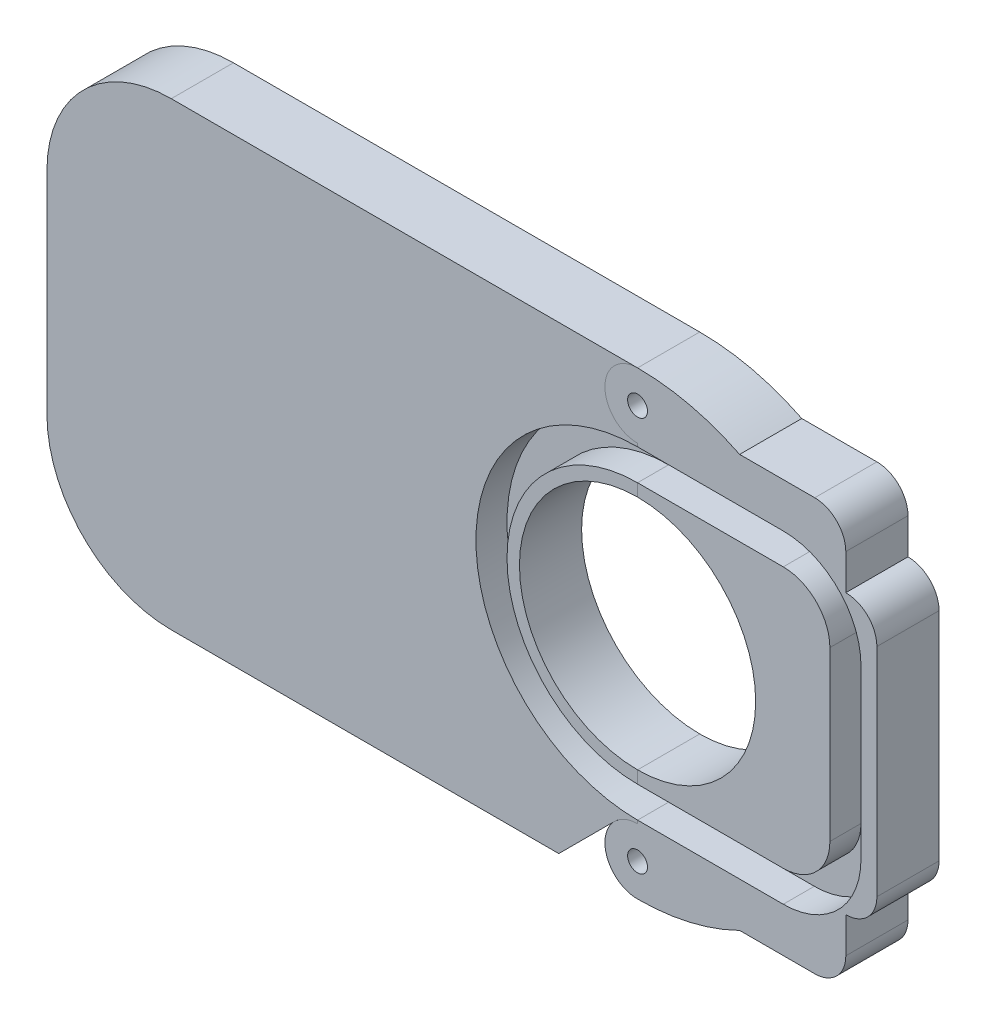
SolidWorks part; units mm, degrees
note: The reader was unsure of these and kept them because the rebuilt part matched: shared geometry of "Sketch1<6>".
material "Сталь 08кп ГОСТ 535-88"
ref_plane "Спереди" through (0, 0, 0) normal (0, 0, 1) x (1, 0, 0)
ref_plane "Сверху" through (0, 0, 0) normal (0, 1, 0) x (1, 0, 0)
ref_plane "Справа" through (0, 0, 0) normal (1, 0, 0) x (0, 0, -1)
sketch "Sketch1" plane through (0, 0, 0) normal (0, 0, 1) x (1, 0, 0)
  line L0 (-51.8389, -200.705) -> (-60.8012, -209.6673)
  line L1 (-14.6282, -195.0926) -> (-14.6282, -200.824)
  line L2 (-19.6282, -205.824) -> (-31.7061, -205.824)
  line L3 (-14.6266, -150.2409) -> (-14.6266, -144.5103)
  line L4 (-19.6266, -139.5103) -> (-31.7068, -139.5103)
  line L26 (-9.6282, -190.0926) -> (-9.6282, -155.2396)
  line L27 (-143.1333, -155.6673) -> (-143.1333, -189.6673)
  line L28 (-123.1333, -209.6673) -> (-60.8012, -209.6673)
  line L32 (-48.1266, -135.6673) -> (-123.1333, -135.6673)
  line L33 (-48.1266, -153.6673) -> (-48.1266, -146.1673)
  line L34 (-48.1266, -199.1673) -> (-48.1266, -191.6673)
  arc A0 (-48.1266, -146.1673) -> (-48.1266, -135.6673) centre (-48.1266, -140.9173) cw
  circle A1 centre (-48.1266, -140.9173) radius 1.6
  arc A2 (-48.1266, -209.6673) -> (-48.1266, -199.1673) centre (-48.1266, -204.4173) cw
  circle A3 centre (-48.1266, -204.4173) radius 1.6
  arc A4 (-14.6266, -144.5103) -> (-19.6266, -139.5103) centre (-19.6266, -144.5103) ccw
  arc A5 (-14.6282, -200.824) -> (-19.6282, -205.824) centre (-19.6282, -200.824) cw
  arc A17 (-9.6282, -155.2396) -> (-14.6266, -150.2409) centre (-14.6282, -155.2409) ccw
  arc A18 (-31.7068, -139.5103) -> (-48.1266, -135.6673) centre (-48.1266, -172.6673) ccw
  arc A31 (-48.1266, -209.6673) -> (-31.7061, -205.824) centre (-48.1266, -172.6673) ccw
  arc A32 (-14.6282, -195.0926) -> (-9.6282, -190.0926) centre (-14.6282, -190.0926) ccw
  arc A33 (-143.1333, -189.6673) -> (-123.1333, -209.6673) centre (-123.1333, -189.6673) ccw
  arc A38 (-123.1333, -135.6673) -> (-143.1333, -155.6673) centre (-123.1333, -155.6673) ccw
  circle A39 centre (-48.1266, -172.6673) radius 19
  dimension "D2" = 3.2
  dimension "D3" = 3.2
  dimension "D4" = 5
extrude "Boss-Extrude1" add sketch "Sketch1" along normal blind 10
extrude "Boss-Extrude2" add sketch "Sketch1<6>" along normal blind 10 separate body
sketch "Sketch1<6>" plane through (0, 0, 0) normal (0, 0, 1) x (1, 0, 0) same geometry as "Sketch1"
sketch "Sketch2" plane through (0, 0, 10) normal (0, 0, -1) x (-1, 0, 0)
  line L2 (48.1266, -151.6673) -> (48.1266, -146.4173)
  line L4 (48.1266, -198.9173) -> (48.1266, -193.6673)
  arc A6 (48.1266, -193.6673) -> (48.1266, -151.6673) centre (48.1266, -172.6673) ccw
  arc A7 (48.1266, -198.6673) -> (48.1266, -146.6673) centre (48.1266, -172.6673) ccw
  line M55 (48.1266, -191.6673) -> (48.1266, -199.1673)
  line M57 (48.1266, -146.1673) -> (48.1266, -153.6673)
extrude "Cut-Extrude3" cut sketch "Sketch2" along normal blind 5 contours A7 A6 M55 M57
sketch "Sketch5" plane through (0, 0, 10) normal (0, 0, 1) x (1, 0, 0)
  line L0 (-48.1266, -198.6673) -> (-48.1266, -193.6673)
  line L2 (-48.1266, -151.6673) -> (-48.1266, -146.6673) construction
  line L3 (-48.1266, -151.6673) -> (-48.1266, -146.6673) construction
  line L4 (-48.1266, -198.6673) -> (-48.1266, -193.6673) construction
  line L5 (-48.1266, -198.6673) -> (-24.6887, -198.6673)
  line L6 (-48.1266, -196.1673) -> (-24.6887, -196.1673) construction
  line L8 (-48.1266, -149.1673) -> (-24.6887, -149.1673) construction
  line L9 (-14.6887, -186.1673) -> (-14.6887, -159.1673) construction
  line L10 (-48.1266, -151.6673) -> (-48.1266, -146.6673)
  line L11 (-12.1887, -186.1673) -> (-12.1887, -159.1673)
  line L12 (-48.1266, -146.6673) -> (-24.6887, -146.6673)
  line L13 (-48.1266, -193.6673) -> (-24.6887, -193.6673)
  line L14 (-17.1887, -186.1673) -> (-17.1887, -159.1673)
  line L15 (-48.1266, -151.6673) -> (-24.6887, -151.6673)
  line L16 (-48.1266, -198.6673) -> (-48.1266, -193.6673) construction
  arc A1 (-48.1266, -146.6673) -> (-48.1266, -198.6673) centre (-48.1266, -172.6673) ccw construction
  arc A3 (-24.6887, -149.1673) -> (-14.6887, -159.1673) centre (-24.6887, -159.1673) cw construction
  arc A4 (-24.6887, -196.1673) -> (-14.6887, -186.1673) centre (-24.6887, -186.1673) ccw construction
  arc A5 (-24.6887, -198.6673) -> (-12.1887, -186.1673) centre (-24.6887, -186.1673) ccw
  arc A6 (-24.6887, -146.6673) -> (-12.1887, -159.1673) centre (-24.6887, -159.1673) cw
  arc A7 (-24.6887, -193.6673) -> (-17.1887, -186.1673) centre (-24.6887, -186.1673) ccw
  arc A8 (-24.6887, -151.6673) -> (-17.1887, -159.1673) centre (-24.6887, -159.1673) cw
  line M7 (-48.1266, -146.1673) -> (-48.1266, -153.6673)
  line M9 (-48.1266, -191.6673) -> (-48.1266, -199.1673)
  dimension "D1" = 10
extrude "Cut-Extrude4" cut sketch "Sketch5" against normal blind 5 contours L15 A8 L14 A7 L13 L5 A5 L11 A6 L12 M9 M7
other "Save Bodies1"
